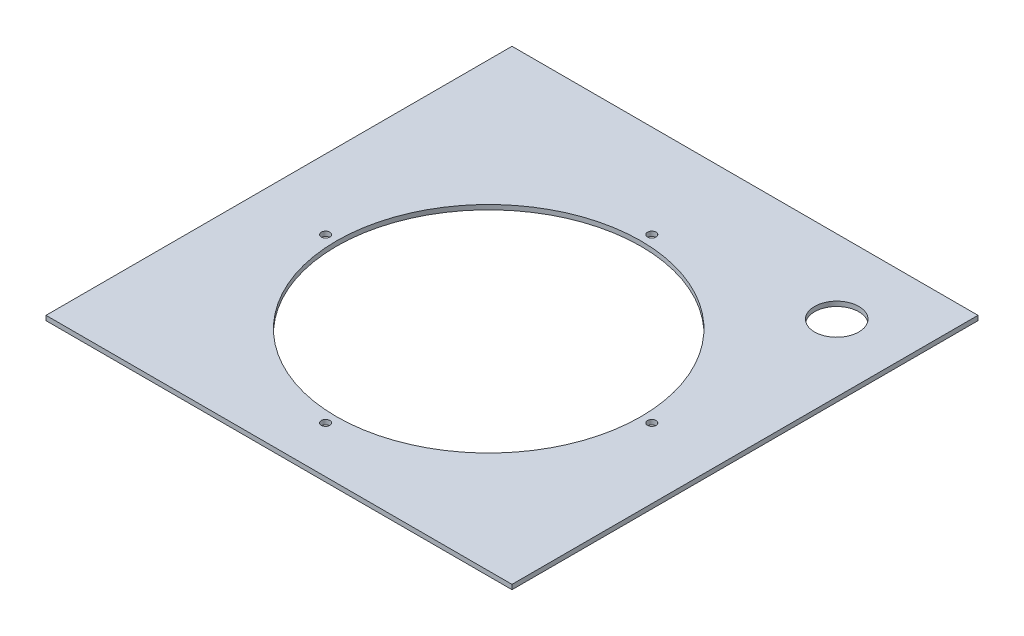
SolidWorks part; units mm, degrees
ref_plane "Front Plane" through (0, 0, 0) normal (0, 0, 1) x (1, 0, 0)
ref_plane "Top Plane" through (0, 0, 0) normal (0, 1, 0) x (1, 0, 0)
ref_plane "Right Plane" through (0, 0, 0) normal (1, 0, 0) x (0, 0, -1)
sketch "Sketch1" plane through (0, 0, 0) normal (0, 1, 0) x (1, 0, 0)
  line L1 (0, 0) -> (300, 0)
  line L2 (0, 0) -> (0, -330)
  line L3 (0, -330) -> (300, -330)
  line L4 (300, 0) -> (300, -330)
  dimension "D1" = 300
  dimension "D2" = 330
extrude "Boss-Extrude1" add sketch "Sketch1" along normal blind 3
sketch "Sketch2" plane through (0, 3, 0) normal (0, 1, 0) x (1, 0, 0)
  line L0 (300, -330) -> (300, 0) construction
  line L1 (0, -330) -> (300, -330) construction
  line L2 (150, -165) -> (300, 0) construction
  circle A0 centre (150, -165) radius 98
  circle A1 centre (256.6859, -47.6455) radius 14.255
  point P2 (0, 0)
  point P5 (300, -165)
  point P8 (150, -330)
  dimension "D1" = 196
  dimension "D3" = 28.51
  dimension "D2" = 158.6
extrude "Cut-Extrude1" cut sketch "Sketch2" against normal up to next
sketch "Sketch4" plane through (0, 3, 0) normal (0, 1, 0) x (1, 0, 0)
  circle A0 centre (150, -165) radius 105 construction
  circle A2 centre (45, -165) radius 2.75
  circle A3 centre (255, -165) radius 2.75
  circle A4 centre (150, -270) radius 2.75
  circle A5 centre (150, -60) radius 2.75
  dimension "D1" = 210
  dimension "D2" = 5.5
  dimension "D3" = 5.5
  dimension "D4" = 5.5
  dimension "D5" = 5.5
extrude "Cut-Extrude3" cut sketch "Sketch4" against normal through all contours A2 | A5 | A3 | A4
sketch "Sketch5" plane through (0, 3, 0) normal (0, 1, 0) x (1, 0, 0)
  line L0 (300, -330) -> (300, 0) construction
  line L1 (0, 0) -> (300, 0)
  line L2 (0, 0) -> (0, -300)
  line L3 (0, -300) -> (300, -300)
  line L4 (300, 0) -> (300, -300)
  line L5 (0, -330) -> (300, -330) construction
  dimension "D1" = 30
sketch "Sketch6" plane through (0, 3, 0) normal (0, 1, 0) x (1, 0, 0)
  line L0 (300, -330) -> (300, 0) construction
  line L1 (0, -330) -> (300, -330)
  line L2 (0, -330) -> (0, -300)
  line L3 (0, -300) -> (300, -300)
  line L4 (300, -330) -> (300, -300)
  dimension "D1" = 30
extrude "Cut-Extrude5" cut sketch "Sketch6" against normal through all
